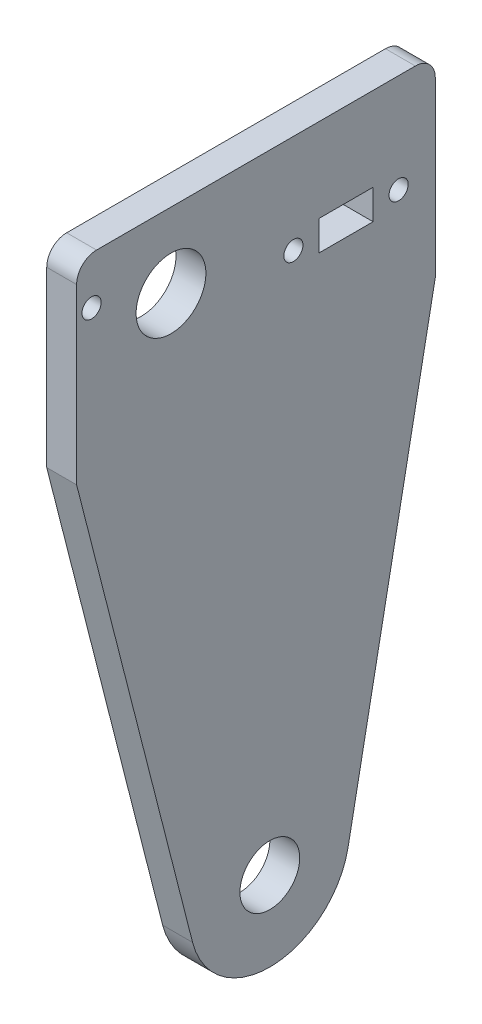
SolidWorks part; units mm, degrees
ref_plane "Front Plane" through (0, 0, 0) normal (0, 0, 1) x (1, 0, 0)
ref_plane "Top Plane" through (0, 0, 0) normal (0, 1, 0) x (1, 0, 0)
ref_plane "Right Plane" through (0, 0, 0) normal (1, 0, 0) x (0, 0, -1)
sketch "Sketch1" plane through (0, 0, 0) normal (1, 0, 0) x (0, 0, -1)
  line L0 (42.1132, 8.7376) -> (42.1132, -18.8943)
  line L1 (-15.0368, 8.7376) -> (-15.0368, -18.8943)
  line L2 (38.9382, 11.9126) -> (-11.8618, 11.9126)
  line L3 (-15.7317, -3.8354) -> (28.7183, -3.8354) construction
  line L4 (-15.0368, -18.8943) -> (3.4424, -91.2913)
  line L5 (42.1132, -18.8943) -> (28.2157, -90.5678)
  line L7 (23.5712, -6.2166) -> (32.2072, -6.2166)
  line L8 (23.5712, -6.2166) -> (23.5712, -1.4541)
  line L9 (-9.4805, 9.4615) -> (-9.4805, 0) construction
  line L10 (-12.8841, 9.4615) -> (-9.4805, 9.4615) construction
  line L11 (23.5712, -1.4541) -> (32.2072, -1.4541)
  line L12 (32.2072, -6.2166) -> (32.2072, -1.4541)
  line L13 (23.5712, -6.2166) -> (32.2072, -1.4541) construction
  line L14 (23.5712, -1.4541) -> (32.2072, -6.2166) construction
  circle A0 centre (15.7479, -88.1503) radius 4.7625
  arc A1 (3.4424, -91.2913) -> (28.2157, -90.5678) centre (15.7479, -88.1503) ccw
  circle A2 centre (0, 0) radius 5.5626
  circle A3 centre (-12.6555, 4.3307) radius 1.524
  arc A4 (42.1132, 8.7376) -> (38.9382, 11.9126) centre (38.9382, 8.7376) ccw
  circle A5 centre (15.7479, -88.1503) radius 77.47 construction
  circle A6 centre (36.2712, -3.8354) radius 1.524
  arc A10 (-15.0368, 8.7376) -> (-11.8618, 11.9126) centre (-11.8618, 8.7376) cw
  circle A11 centre (19.5072, -3.8354) radius 1.524
  circle A12 centre (2.7432, -3.8354) radius 1.524 [skipped]
  circle A13 centre (-14.0208, -3.8354) radius 1.524 [skipped]
  point P21 (27.8892, -3.8354)
  dimension "D1" = 3.175
  dimension "D2" = 12.7
  dimension "D3" = 154.94
  dimension "D4" = 11.1252
  dimension "D6" = 3.048
  dimension "D9" = 3.048
  dimension "D13" = 5.1308
  dimension "D15" = 9.525
  dimension "D5" = 11.9126
  dimension "D8" = 5.842
  dimension "D10" = 2.3813
  dimension "D11" = 15.748
  dimension "D12" = 5.5562
  dimension "D14" = 57.15
  dimension "D16" = 4.7625
  dimension "D17" = 8.382
  dimension "D18" = 8.636
  dimension "D7" = 2
extrude "Boss-Extrude1" add sketch "Sketch1" along normal blind 4.7625
